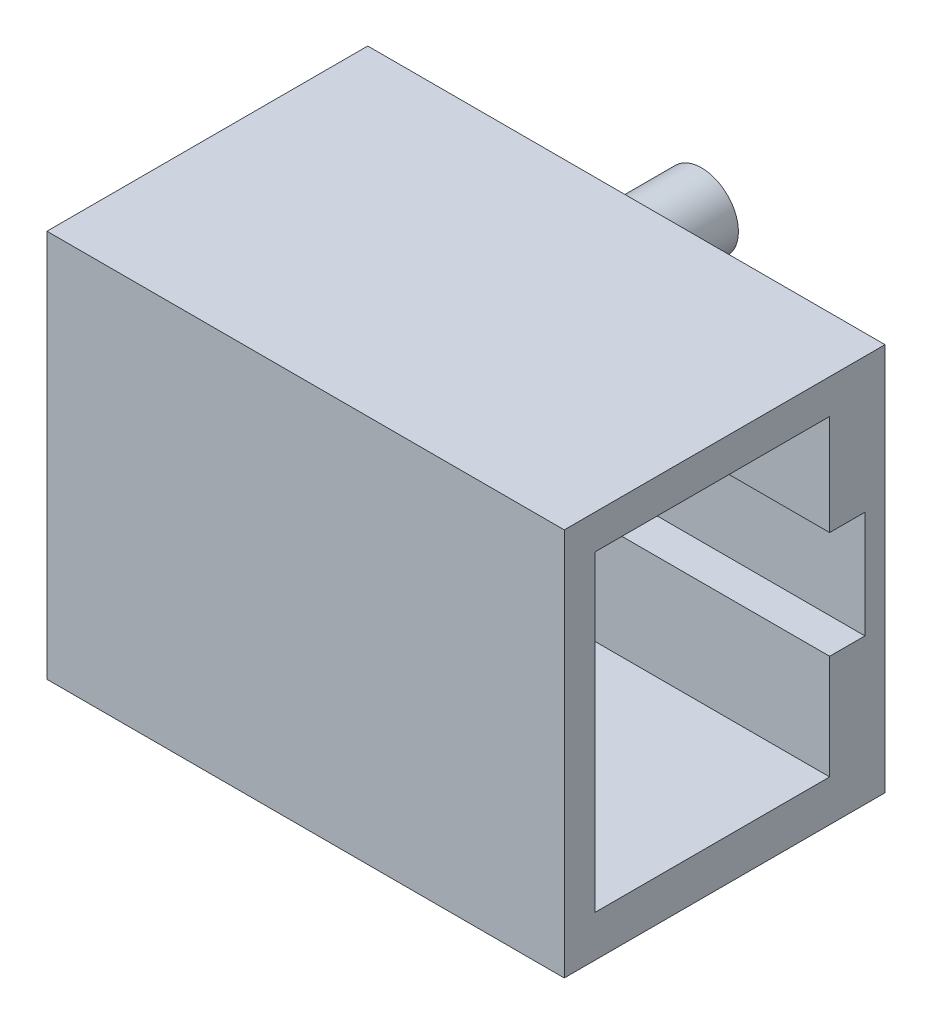
SolidWorks part; units mm, degrees
ref_plane "Front" through (0, 0, 0) normal (0, 0, 1) x (1, 0, 0)
ref_plane "Top" through (0, 0, 0) normal (0, 1, 0) x (1, 0, 0)
ref_plane "Right" through (0, 0, 0) normal (1, 0, 0) x (0, 0, -1)
sketch "Sketch1" plane through (0, 0, 0) normal (0, 0, 1) x (1, 0, 0)
  line L1 (0, 0) -> (21.06, 0)
  line L2 (0, 0) -> (0, -15.8)
  line L3 (0, -15.8) -> (21.06, -15.8)
  line L4 (21.06, 0) -> (21.06, -15.8)
  dimension "D1" = 21.06
  dimension "D2" = 15.8
extrude "Extrude1" add sketch "Sketch1" along normal blind 13.06
sketch "Sketch2" plane through (0, 0, 0) normal (0, 0, -1) x (-1, 0, 0)
  line L0 (-21.06, -15.8) -> (-21.06, 0) construction
  line L1 (0, -15.8) -> (-21.06, -15.8) construction
  circle A0 centre (-10.34, -2.25) radius 1.5
  circle A1 centre (-10.34, -13.68) radius 1.5
  dimension "D1" = 3
  dimension "D2" = 3
  dimension "D3" = 10.72
  dimension "D4" = 10.72
  dimension "D5" = 11.43
  dimension "D6" = 2.12
extrude "Extrude2" add sketch "Sketch2" along normal blind 3.25
sketch "Sketch3" plane through (21.06, 0, 0) normal (1, 0, 0) x (0, 0, -1)
  line L0 (-11.8095, -14.1132) -> (-11.8095, -1.4032)
  line L1 (-11.8095, -1.4032) -> (-2.2549, -1.4032)
  line L2 (-2.2549, -1.4032) -> (-2.2549, -5.498)
  line L3 (-2.2549, -5.498) -> (-0.819, -5.498)
  line L4 (-0.819, -5.498) -> (-0.819, -9.8588)
  line L5 (-0.819, -9.8588) -> (-2.2549, -9.8588)
  line L6 (-2.2549, -9.8588) -> (-2.2549, -14.1132)
  line L7 (-2.2549, -14.1132) -> (-11.8095, -14.1132)
extrude "Cut-Extrude1" cut sketch "Sketch3" against normal blind 18
